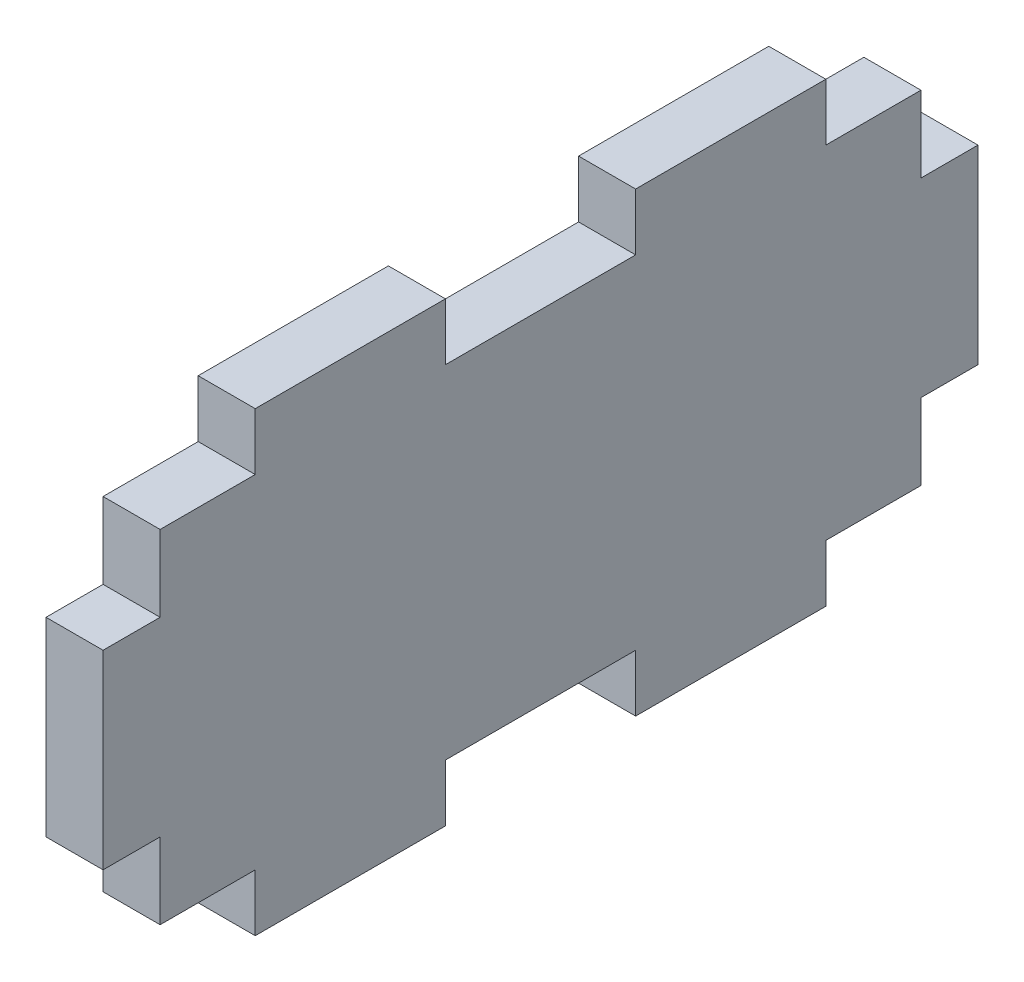
SolidWorks part; units mm, degrees
material "PC High Viscosity"
ref_plane "Front Plane" through (0, 0, 0) normal (0, 0, 1) x (1, 0, 0)
ref_plane "Top Plane" through (0, 0, 0) normal (0, 1, 0) x (1, 0, 0)
ref_plane "Right Plane" through (0, 0, 0) normal (1, 0, 0) x (0, 0, -1)
sketch "Sketch1" plane through (0, 0, 0) normal (1, 0, 0) x (0, 0, -1)
  line L1 (-23, -12) -> (23, -12)
  line L2 (-23, -12) -> (-23, 12)
  line L3 (-23, 12) -> (23, 12)
  line L4 (23, -12) -> (23, 12)
  line L5 (-23, -12) -> (23, 12) construction
  line L6 (-23, 12) -> (23, -12) construction
  point P0 (0, 0)
  dimension "D1" = 46
  dimension "D2" = 24
extrude "Boss-Extrude1" add sketch "Sketch1" along normal blind 3 contours L3 L4 L1 L2
sketch "Sketch2" plane through (3, 0, 0) normal (1, 0, 0) x (0, 0, -1)
  line L0 (23, -12) -> (23, 12) construction
  line L1 (23, 5) -> (20, 5)
  line L2 (23, 5) -> (23, -5) construction
  line L3 (23, -5) -> (20, -5) construction
  line L4 (20, 5) -> (20, -5) construction
  line L5 (0, 0) -> (23, 0) construction
  line L6 (20, 5) -> (20, 9)
  line L7 (20, 9) -> (15, 9)
  line L8 (15, 9) -> (15, 12)
  line L9 (-23, 12) -> (23, 12) construction
  line L10 (15, 12) -> (23, 12)
  line L11 (23, 12) -> (23, 5)
  line L13 (0, 12) -> (5, 12)
  line L14 (0, 12) -> (0, 9)
  line L15 (0, 9) -> (5, 9)
  line L16 (5, 12) -> (5, 9)
  dimension "D1" = 10
  dimension "D2" = 3
  dimension "D3" = 8
  dimension "D4" = 5
extrude "Cut-Extrude1" cut sketch "Sketch2" against normal through all
mirror "Mirror1" about plane through (0, 0, 0) normal (0, 1, 0) of "Cut-Extrude1"
mirror "Mirror2" about plane through (0, 0, 0) normal (0, 0, 1) of "Mirror1"
equation "\"pulley_pitch_diam\"= 12.73mm"
equation "\"pulley_total_width\"= 16mm"
equation "\"pulley_total_diam\"= 16mm"
equation "\"belt_width\"= 6mm"
equation "\"material_thickness\"= 3mm"
equation "\"shaft_diam\"= 8mm"
equation "\"bearing_od\"= 22mm"
equation "\"bearing_thickness\"= 7mm"
equation "\"D1@Boss-Extrude1\"=\"material_thickness\""
equation "\"D2@Sketch2\"=\"material_thickness\""
